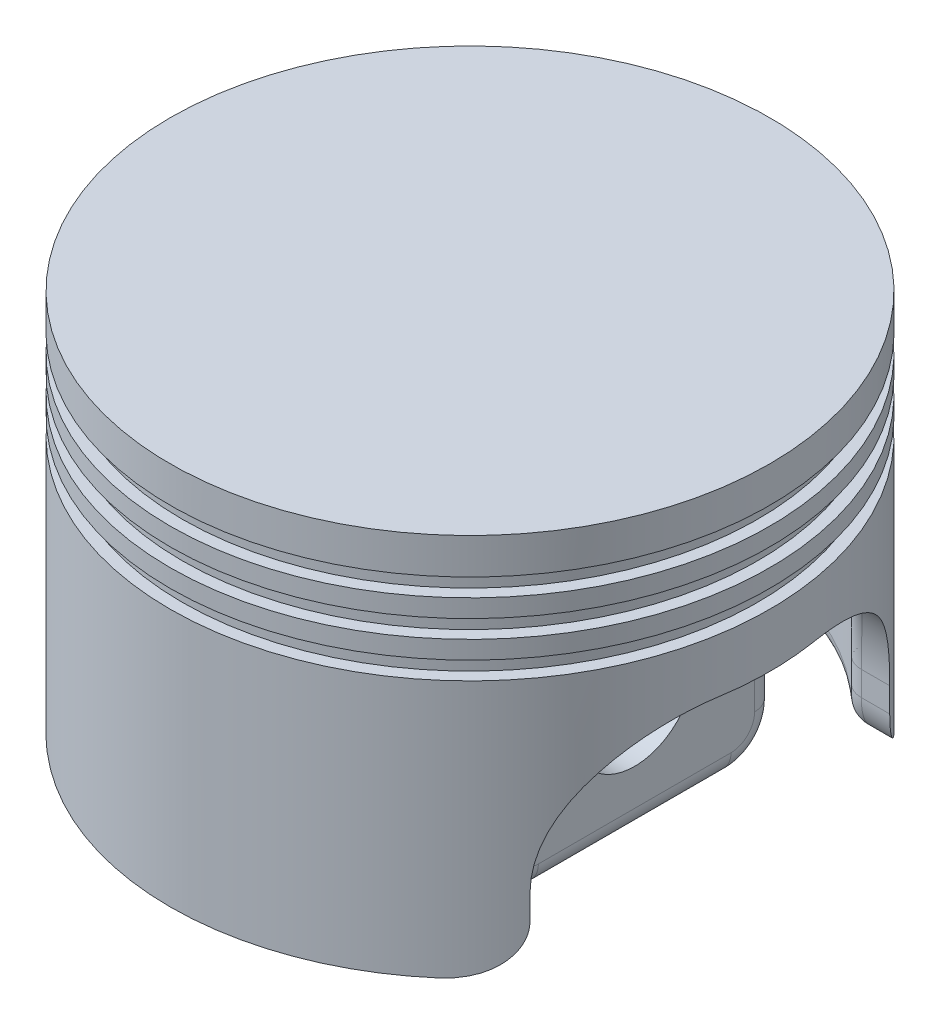
SolidWorks part; units mm, degrees
ref_plane "Front Plane" through (0, 0, 0) normal (0, 0, 1) x (1, 0, 0)
ref_plane "Top Plane" through (0, 0, 0) normal (0, 1, 0) x (1, 0, 0)
ref_plane "Right Plane" through (0, 0, 0) normal (1, 0, 0) x (0, 0, -1)
sketch "Sketch1" plane through (0, 0, 0) normal (0, 0, 1) x (1, 0, 0)
  line L0 (0, 0) -> (0, -19)
  line L1 (0, -19) -> (57.15, -19)
  line L2 (57.15, -19) -> (57.15, -81.28)
  line L3 (57.15, -81.28) -> (63.5, -81.28)
  line L4 (63.5, -81.28) -> (63.5, 0)
  line L5 (63.5, 0) -> (0, 0)
  dimension "D1" = 63.5
  dimension "D2" = 81.28
  dimension "D3" = 19
  dimension "D4" = 57.15
revolve "Revolve1" add sketch "Sketch1" angle 360 about L0
sketch "Sketch2" plane through (0, 0, 0) normal (1, 0, 0) x (0, 0, -1)
  line L0 (-63.5, -81.28) -> (63.5, -81.28) construction
  line L1 (-38.1, -38.1) -> (38.1, -38.1)
  line L2 (-38.1, -38.1) -> (-38.1, -81.28)
  line L3 (-38.1, -81.28) -> (38.1, -81.28)
  line L4 (38.1, -38.1) -> (38.1, -81.28)
  line L5 (-38.1, -38.1) -> (38.1, -81.28) construction
  line L6 (-38.1, -81.28) -> (38.1, -38.1) construction
  point P0 (0, -59.69)
  dimension "D1" = 76.2
  dimension "D2" = 43.18
extrude "Cut-Extrude1" cut sketch "Sketch2" against normal through all both and the other way through all
sketch "Sketch3" plane through (0, 0, 0) normal (1, 0, 0) x (0, 0, -1)
  line L0 (0, 0) -> (0, -16.9123) construction
  line L1 (63.5, -81.28) -> (63.5, 0) construction
  line L2 (60.96, -7.62) -> (66.04, -7.62)
  line L3 (60.96, -7.62) -> (60.96, -11.43)
  line L4 (60.96, -11.43) -> (66.04, -11.43)
  line L5 (66.04, -7.62) -> (66.04, -11.43)
  line L6 (60.96, -7.62) -> (66.04, -11.43) construction
  line L7 (60.96, -11.43) -> (66.04, -7.62) construction
  line L8 (63.5, 0) -> (-63.5, 0) construction
  point P3 (63.5, -9.525)
  dimension "D1" = 3.81
  dimension "D2" = 2.54
  dimension "D3" = 7.62
revolve "Cut-Revolve1" cut sketch "Sketch3" angle 360 about L0
pattern_linear "LPattern1" count 3 spacing 7.62 along (0, -1, 0) of "Cut-Revolve1"
sketch "Sketch6" plane through (0, -19, 0) normal (0, -1, 0) x (1, 0, 0)
  line L0 (0, 0) -> (0, 32.219) construction
  line L1 (34.88, -30.4) -> (15.88, 30.4) construction
  line L2 (-34.88, 30.4) -> (-15.88, 30.4)
  line L3 (-34.88, 30.4) -> (-34.88, -30.4)
  line L4 (-34.88, -30.4) -> (-15.88, -30.4)
  line L5 (-15.88, 30.4) -> (-15.88, -30.4)
  line L6 (-34.88, 30.4) -> (-15.88, -30.4) construction
  line L7 (-34.88, -30.4) -> (-15.88, 30.4) construction
  line L8 (34.88, 30.4) -> (15.88, -30.4) construction
  line L9 (34.88, -30.4) -> (15.88, -30.4)
  line L10 (34.88, 30.4) -> (15.88, 30.4)
  line L11 (15.88, 30.4) -> (15.88, -30.4)
  line L12 (34.88, 30.4) -> (34.88, -30.4)
  point P3 (-25.38, 0)
  dimension "D1" = 19
  dimension "D2" = 60.8
  dimension "D3" = 31.76
extrude "Boss-Extrude1" add sketch "Sketch6" along normal blind 63.5
sketch "Sketch7" plane through (34.88, 0, 0) normal (1, 0, 0) x (0, 0, -1)
  line L0 (30.4, -82.5) -> (-30.4, -82.5) construction
  circle A0 centre (0, -57.1) radius 12.7
  dimension "D1" = 25.4
  dimension "D2" = 25.4
extrude "Cut-Extrude2" cut sketch "Sketch7" against normal through all and the other way through all
fillet "Fillet1" radius 28 4 edges at (-46.6985, -38.1, -38.1) (-46.6985, -38.1, 38.1) (46.6985, -38.1, -38.1) (46.6985, -38.1, 38.1)
fillet "Fillet2" radius 10 8 edges at (46.6985, -81.28, -38.1) (46.6985, -81.28, 38.1) (-46.6985, -81.28, 38.1) (-46.6985, -81.28, -38.1) (25.38, -82.5, 30.4) (25.38, -82.5, -30.4) (-25.38, -82.5, -30.4) (-25.38, -82.5, 30.4)
fillet "Fillet3" radius 5 36 edges at (-15.88, -45.75, -30.4) (-15.88, -79.5711, -27.4711) (-15.88, -45.75, 30.4) (-15.88, -79.5711, 27.4711) (-34.88, -45.75, 30.4) (-34.88, -79.5711, 27.4711) (-34.88, -45.75, -30.4) (-34.88, -79.5711, -27.4711) (15.88, -45.75, 30.4) (15.88, -79.5711, 27.4711) (15.88, -45.75, -30.4) (15.88, -79.5711, -27.4711) (34.88, -45.75, -30.4) (34.88, -79.5711, -27.4711) (34.88, -45.75, 30.4) (34.88, -79.5711, 27.4711) (40.0022, -78.1316, -40.816) (42.5971, -68.69, -38.1) (46.055, -51.2516, -33.8387) (57.15, -38.1, 0) (50.4318, -43.6881, 26.8841) (42.5971, -68.69, 38.1) (41.3657, -76.2692, 39.4335) (0, -81.28, 57.15) (-40.0022, -78.1316, 40.816) (-42.5971, -68.69, 38.1) (-46.055, -51.2516, 33.8387) (-57.15, -38.1, 0) (-50.4318, -43.6881, -26.8841) (-42.5971, -68.69, -38.1) (-41.3657, -76.2692, -39.4335) (-15.88, -82.5, 0) (-34.88, -82.5, 0) (15.88, -82.5, 0) (34.88, -82.5, 0) (0, -81.28, -57.15)
fillet "Fillet4" radius 5 17 edges at (33.4155, -19, 28.9355) (25.38, -19, 30.4) (17.3445, -19, 28.9355) (15.88, -19, 0) (17.3445, -19, -28.9355) (25.38, -19, -30.4) (33.4155, -19, -28.9355) (34.88, -19, 0) (-57.15, -19, 0) (-17.3445, -19, 28.9355) (-25.38, -19, 30.4) (-33.4155, -19, 28.9355) (-34.88, -19, 0) (-33.4155, -19, -28.9355) (-25.38, -19, -30.4) (-17.3445, -19, -28.9355) (-15.88, -19, 0)
